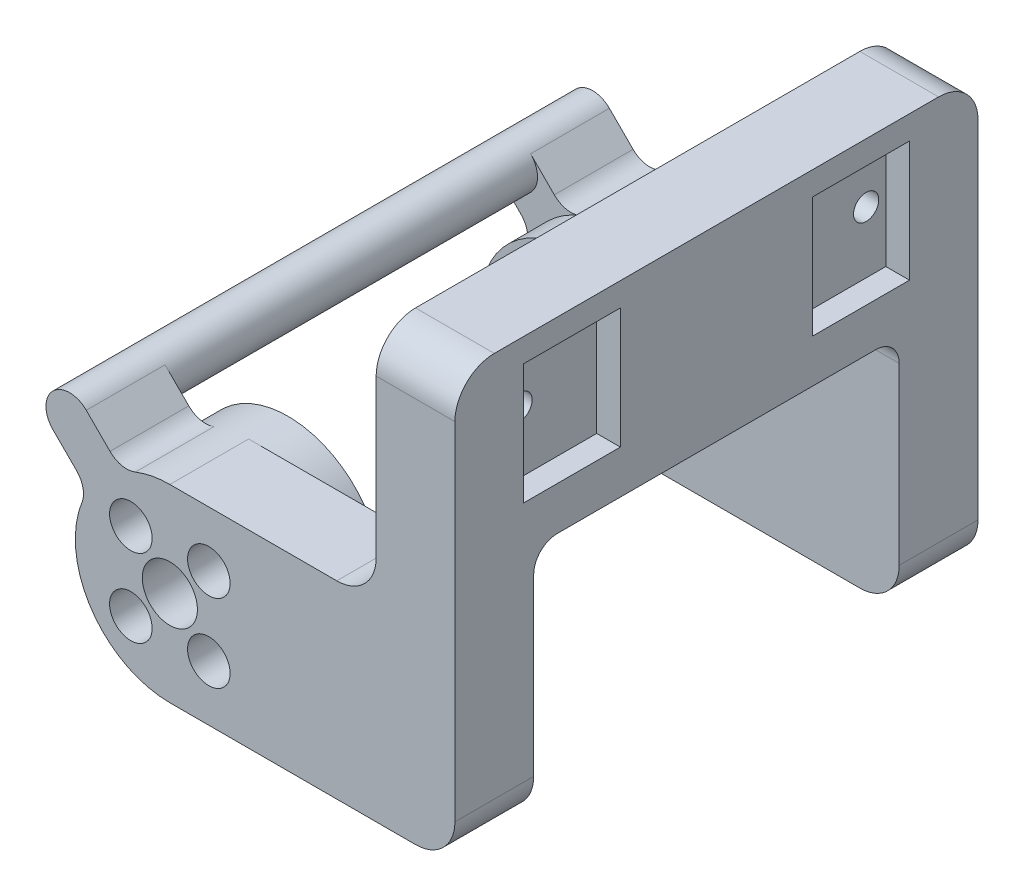
SolidWorks part; units mm, degrees
ref_plane "前视基准面" through (0, 0, 0) normal (0, 0, 1) x (1, 0, 0)
ref_plane "上视基准面" through (0, 0, 0) normal (0, 1, 0) x (1, 0, 0)
ref_plane "右视基准面" through (0, 0, 0) normal (1, 0, 0) x (0, 0, -1)
other "Configuration Table"
sketch "草图1" plane through (0, 0, 0) normal (0, 0, 1) x (1, 0, 0)
  line L0 (0, 12) -> (36.1853, 12)
  line L1 (36.1853, 12) -> (36.1853, -12)
  line L2 (36.1853, -12) -> (0, -12)
  arc A0 (0, 12) -> (0, -12) centre (0, 0) ccw
  dimension "D1" = 36.1853
extrude "凸台-拉伸1" add sketch "草图1" along normal blind 13.5
ref_plane "基准面1" through (0, 0, -16.7) normal (0, 0, -1) x (-1, 0, 0)
sketch "草图5" plane through (0, 0, 0) normal (0, 0, -1) x (-1, 0, 0)
  circle A0 centre (0, 0) radius 10.1
extrude "切除-拉伸2" cut sketch "草图5" against normal blind 1.5
sketch "草图7" plane through (0, 0, 1.5) normal (0, 0, -1) x (-1, 0, 0)
  circle A0 centre (0, 0) radius 3.5
extrude "切除-拉伸3" cut sketch "草图7" against normal blind 37
sketch "草图9" plane through (0, 0, 1.5) normal (0, 0, -1) x (-1, 0, 0)
  line L0 (-4.9497, 4.9497) -> (0, 0) construction
  line L1 (0, 0) -> (0, 7.7766) construction
  circle A0 centre (-4.9497, 4.9497) radius 1.5
  circle A1 centre (4.9497, 4.9497) radius 1.5
  circle A2 centre (4.9497, -4.9497) radius 1.5
  circle A3 centre (-4.9497, -4.9497) radius 1.5
  point P14 (0, 0)
  dimension "D1" = 7
  dimension "D2" = 45
  dimension "D3" = 4
extrude "切除-拉伸4" cut sketch "草图9" against normal blind 24.5
mirror "镜向14" about plane through (0, 0, -16.7) normal (0, 0, -1) of bodies 111
sketch "草图11" plane through (36.1853, 0, 0) normal (1, 0, 0) x (0, 0, -1)
  line L1 (-13.5, 12) -> (46.9, 12)
  line L2 (-13.5, 12) -> (-13.5, -12)
  line L3 (-13.5, -12) -> (46.9, -12)
  line L4 (46.9, 12) -> (46.9, -12)
extrude "凸台-拉伸2" add sketch "草图11" against normal blind 10
sketch "草图12" plane through (0, 0, 13.5) normal (0, 0, 1) x (1, 0, 0)
  circle A0 centre (4.9497, 4.9497) radius 2.7
  circle A1 centre (4.9497, -4.9497) radius 2.7
  circle A2 centre (-4.9497, -4.9497) radius 2.7
  circle A3 centre (-4.9497, 4.9497) radius 2.7
  point P12 (0, 0)
  dimension "D1" = 4
extrude "切除-拉伸5" cut sketch "草图12" against normal blind 8.5
sketch "草图18" plane through (0, 0, 0) normal (0, 0, -1) x (-1, 0, 0)
  circle A0 centre (0, 0) radius 12
extrude "切除-拉伸9" cut sketch "草图18" against normal blind 1.5
sketch "草图19" plane through (0, 0, 1.5) normal (0, 0, -1) x (-1, 0, 0)
  line L4 (0, 0) -> (7.3362, 0) construction
  line L5 (14.6724, -3) -> (0, -3)
  line L6 (14.6724, -3) -> (14.6724, 3)
  line L7 (14.6724, 3) -> (0, 3)
  line L8 (0, -3) -> (0, 3)
  line L9 (14.6724, -3) -> (0, 3) construction
  line L10 (14.6724, 3) -> (0, -3) construction
  point P0 (7.3362, 0)
  dimension "D1" = 6
extrude "切除-拉伸10" cut sketch "草图19" against normal blind 3
sketch "草图20" plane through (0, 0, 13.5) normal (0, 0, 1) x (1, 0, 0)
  line L1 (-17.9701, 18.7991) -> (58.5374, 18.7991)
  line L2 (-17.9701, 18.7991) -> (-17.9701, -18.303)
  line L3 (-17.9701, -18.303) -> (58.5374, -18.303)
  line L4 (58.5374, 18.7991) -> (58.5374, -18.303)
extrude "切除-拉伸11" cut sketch "草图20" against normal blind 3.5
mirror "镜向24" about plane through (0, 0, -16.7) normal (0, 0, -1) of "切除-拉伸5", "切除-拉伸9", "切除-拉伸10"
mirror "镜向26" about plane through (0, 0, -16.7) normal (0, 0, -1) of "切除-拉伸11"
sketch "草图21" plane through (0, 0, -43.4) normal (0, 0, -1) x (-1, 0, 0)
  line L3 (0, 12) -> (-36.1853, 12)
  line L4 (-36.1853, 12) -> (-36.1853, -12)
  line L5 (-36.1853, -12) -> (0, -12)
  line L6 (0, 12) -> (-36.1853, 12)
  line L7 (-36.1853, 12) -> (-36.1853, -12)
  line L8 (-36.1853, -12) -> (0, -12)
  circle A0 centre (4.9497, -4.9497) radius 2.7 construction
  arc A1 (0, -12) -> (0, 12) centre (0, 0) ccw
  arc A2 (0, -12) -> (0, 12) centre (0, 0) ccw
  circle A3 centre (0, 0) radius 3.5 construction
  circle A4 centre (4.9497, 4.9497) radius 2.7 construction
  circle A5 centre (-4.9497, 4.9497) radius 2.7 construction
  circle A6 centre (4.9497, -4.9497) radius 2.7
  circle A7 centre (0, 0) radius 3.5
  circle A8 centre (4.9497, 4.9497) radius 2.7
  circle A9 centre (-4.9497, 4.9497) radius 2.7
  circle A10 centre (-4.9497, -4.9497) radius 2.7 construction
  circle A11 centre (-4.9497, -4.9497) radius 2.7
  dimension "D1" = 0
extrude "凸台-拉伸3" add sketch "草图21" along normal blind 6.5
sketch "草图22" plane through (0, 0, -33.4) normal (0, 0, 1) x (1, 0, 0)
  line L3 (0, -12) -> (26.1853, -12)
  line L4 (26.1853, -12) -> (26.1853, 12)
  line L5 (26.1853, 12) -> (0, 12)
  line L6 (0, -12) -> (26.1853, -12)
  line L7 (26.1853, -12) -> (26.1853, 12)
  line L8 (26.1853, 12) -> (0, 12)
  arc A1 (0, -12) -> (0, 12) centre (0, 0) ccw
  arc A2 (0, -12) -> (0, 12) centre (0, 0) ccw
  dimension "D1" = 0
extrude "切除-拉伸12" cut sketch "草图22" against normal blind 6.5
mirror "镜向27" about plane through (0, 0, -16.7) normal (0, 0, -1) of "切除-拉伸12", "凸台-拉伸3"
sketch "草图23" plane through (36.1853, 0, 0) normal (1, 0, 0) x (0, 0, -1)
  line L0 (49.9, 12) -> (49.9, -12) construction
  line L1 (-16.5, 12) -> (49.9, 12)
  line L2 (-16.5, 12) -> (-16.5, 42)
  line L3 (-16.5, 42) -> (49.9, 42)
  line L4 (49.9, 12) -> (49.9, 42)
  dimension "D1" = 30
  dimension "D2" = 0
extrude "凸台-拉伸4" add sketch "草图23" against normal up to surface (10 mm away) up to face at (26.1853, 0, -16.7)
sketch "草图24" plane through (26.1853, 0, 0) normal (-1, 0, 0) x (0, 0, 1)
  line L0 (-39.9, -12) -> (-39.9, 12) construction
  line L5 (-39.9, 18.2) -> (6.5, 18.2)
  line L6 (-39.9, 18.2) -> (-39.9, -12)
  line L7 (-39.9, -12) -> (6.5, -12)
  line L8 (6.5, 18.2) -> (6.5, -12)
  line L9 (-49.9, 12) -> (-39.9, 12) construction
  dimension "D1" = 0
  dimension "D2" = 6.2
extrude "切除-拉伸13" cut sketch "草图24" against normal blind 58
sketch "草图25" plane through (36.1853, 0, 0) normal (1, 0, 0) x (0, 0, -1)
  line L0 (16.7, -55) -> (16.7, 55) construction
  line L1 (28.9, 39) -> (41.2, 39)
  line L2 (28.9, 39) -> (28.9, 23.7)
  line L3 (28.9, 23.7) -> (41.2, 23.7)
  line L4 (41.2, 39) -> (41.2, 23.7)
  line L5 (49.9, 42) -> (-16.5, 42) construction
  line L6 (4.5, 39) -> (4.5, 23.7)
  line L7 (4.5, 23.7) -> (-7.8, 23.7)
  line L8 (-7.8, 39) -> (-7.8, 23.7)
  line L9 (4.5, 39) -> (-7.8, 39)
  dimension "D1" = 12.3
  dimension "D2" = 15.3
  dimension "D3" = 24.5
  dimension "D4" = 3
extrude "切除-拉伸14" cut sketch "草图25" against normal blind 3
sketch "草图26" plane through (33.1853, 0, 0) normal (1, 0, 0) x (0, 0, -1)
  line L0 (41.2, 23.7) -> (41.2, 39) construction
  line L1 (41.2, 39) -> (28.9, 39) construction
  circle A0 centre (38.7, 31.5) radius 1.6
  dimension "D1" = 2.5
  dimension "D2" = 7.5
extrude "切除-拉伸15" cut sketch "草图26" against normal blind 22
mirror "镜向28" about plane through (0, 0, -16.7) normal (0, 0, -1) of "切除-拉伸15"
fillet "圆角1" radius 5 6 edges at (31.1853, 42, 16.5) (31.1853, 42, -49.9) (36.1853, -12, 11.5) (36.1853, -12, -44.9) (26.1853, 12, 11.5) (26.1853, 12, -44.9)
fillet "圆角2" radius 3 2 edges at (31.1853, 18.2, -39.9) (31.1853, 18.2, 6.5)
sketch "草图27" plane through (0, 0, 16.5) normal (0, 0, 1) x (1, 0, 0)
  line L0 (-14.8492, 10.6066) -> (-10.3372, 6.0945)
  line L5 (0, 0) -> (-4.9497, 4.9497) construction
  line L6 (-4.9497, 4.9497) -> (-10.6066, 10.6066) construction
  line L9 (-10.6066, 14.8492) -> (-6.0945, 10.3372)
  arc A1 (0, 12) -> (0, -12) centre (0, 0) ccw construction
  arc A3 (-6.0945, 10.3372) -> (-10.3372, 6.0945) centre (0, 0) ccw
  arc A4 (-14.8492, 10.6066) -> (-10.6066, 14.8492) centre (-12.7279, 12.7279) ccw
  dimension "D2" = 11
extrude "凸台-拉伸5" add sketch "草图27" against normal up to surface (10 mm away) up to face at (23.4461, 3.0916, 6.5)
sketch "草图28" plane through (0, 0, 16.5) normal (0, 0, 1) x (1, 0, 0)
  circle A1 centre (-12.7279, 12.7279) radius 3
extrude "凸台-拉伸6" add sketch "草图28" against normal up to surface (66.4 mm away) up to face at (2.2497, 4.9497, -49.9)
sketch "草图29" plane through (0, 0, -49.9) normal (0, 0, -1) x (-1, 0, 0)
  line L4 (14.8492, 10.6066) -> (10.3372, 6.0945) construction
  line L5 (6.0945, 10.3372) -> (10.6066, 14.8492) construction
  line L6 (14.8492, 10.6066) -> (10.3372, 6.0945)
  line L7 (6.0945, 10.3372) -> (10.6066, 14.8492)
  circle A4 centre (12.7279, 12.7279) radius 3 construction
  arc A5 (10.3372, 6.0945) -> (6.0945, 10.3372) centre (0, 0) ccw construction
  arc A6 (14.8492, 10.6066) -> (10.6066, 14.8492) centre (12.7279, 12.7279) ccw
  arc A7 (10.3372, 6.0945) -> (6.0945, 10.3372) centre (0, 0) ccw
extrude "凸台-拉伸7" add sketch "草图29" against normal up to surface (10 mm away) up to face at (23.4461, 3.0916, -39.9)
fillet "圆角3" radius 3 4 edges at (-10.3372, 6.0945, 11.5) (-10.3372, 6.0945, -44.9) (-6.0945, 10.3372, 11.5) (-6.0945, 10.3372, -44.9)
